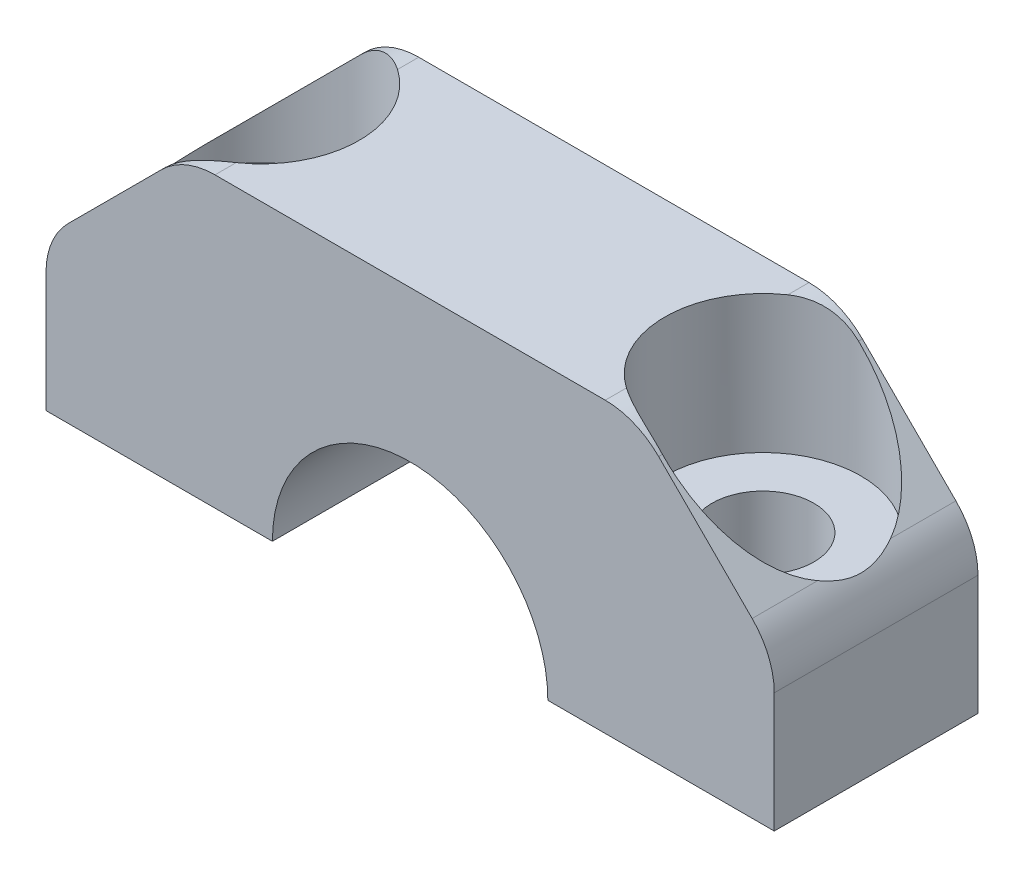
SolidWorks part; units mm, degrees
ref_plane "Front Plane" through (0, 0, 0) normal (0, 0, 1) x (1, 0, 0)
ref_plane "Top Plane" through (0, 0, 0) normal (0, 1, 0) x (1, 0, 0)
ref_plane "Right Plane" through (0, 0, 0) normal (1, 0, 0) x (0, 0, -1)
sketch "Sketch2" plane through (0, 0, 0) normal (0, 0, 1) x (1, 0, 0)
  line L0 (-12.2555, 9.7155) -> (12.2555, 9.7155)
  line L1 (12.2555, 9.7155) -> (12.2555, 0)
  line L2 (12.2555, 0) -> (4.6355, 0)
  line L3 (-12.2555, 9.7155) -> (-12.2555, 0)
  line L4 (-12.2555, 0) -> (-4.6355, 0)
  arc A0 (4.6355, 0) -> (-4.6355, 0) centre (0, 0) ccw
  point P9 (-4.6355, 0)
  point P10 (4.6355, 0)
  point P14 (0, 4.6355)
  dimension "D2" = 9.271
  dimension "D1" = 5.08
  dimension "D3" = 7.62
extrude "Boss-Extrude1" add sketch "Sketch2" along normal blind 6.858
sketch "Sketch3" plane through (0, 0, 0) normal (0, -1, 0) x (1, 0, 0)
  line L0 (-8.4455, 3.429) -> (-8.4455, 0) construction
  line L1 (-12.2555, 0) -> (-4.6355, 0) construction
  line L2 (-8.4455, 3.429) -> (-8.4455, 6.858) construction
  line L3 (-12.2555, 6.858) -> (-4.6355, 6.858) construction
  line L4 (8.4455, 3.429) -> (8.4455, 0) construction
  line L5 (4.6355, 0) -> (12.2555, 0) construction
  circle A0 centre (-8.4455, 3.429) radius 1.7145
  circle A1 centre (8.4455, 3.429) radius 1.7145
  dimension "D1" = 3.429
extrude "Cut-Extrude1" cut sketch "Sketch3" against normal through all and the other way through all
sketch "Sketch4" plane through (0, 0, 6.858) normal (0, 0, 1) x (1, 0, 0)
  line L0 (-12.2555, 5.08) -> (-7.62, 9.7155)
  line L2 (12.2555, 9.7155) -> (-12.2555, 9.7155) construction
  line L3 (-7.62, 9.7155) -> (-12.2555, 9.7155)
  line L4 (-12.2555, 9.7155) -> (-12.2555, 5.08)
  line L5 (12.2555, 9.7155) -> (7.62, 9.7155)
  line L6 (7.62, 9.7155) -> (12.2555, 5.08)
  line L8 (12.2555, 5.08) -> (12.2555, 9.7155)
  point P2 (-9.7155, 4.7786)
  point P3 (9.7155, 4.6355)
  dimension "D1" = 5.08
  dimension "D2" = 45
extrude "Cut-Extrude2" cut sketch "Sketch4" against normal through all
ref_plane "Plane1" through (0, 5.08, 0) normal (0, 1, 0) x (1, 0, 0)
sketch "Sketch5" plane through (0, 5.08, 0) normal (0, 1, 0) x (1, 0, 0)
  circle A0 centre (-8.4455, -3.429) radius 3.302
  circle A1 centre (8.4455, -3.429) radius 3.302
  circle A2 centre (-8.4455, -3.429) radius 1.7145 construction
  circle A3 centre (8.4455, -3.429) radius 1.7145 construction
  dimension "D1" = 6.604
extrude "Cut-Extrude3" cut sketch "Sketch5" along normal through all
fillet "Fillet1" radius 2.54 4 edges at (7.62, 9.7155, 0.1159) (7.62, 9.7155, 6.7421) (-7.62, 9.7155, 6.7421) (-7.62, 9.7155, 0.1159)
fillet "Fillet2" radius 2.54 2 edges at (12.2555, 5.08, 3.429) (-12.2555, 5.08, 3.429)
